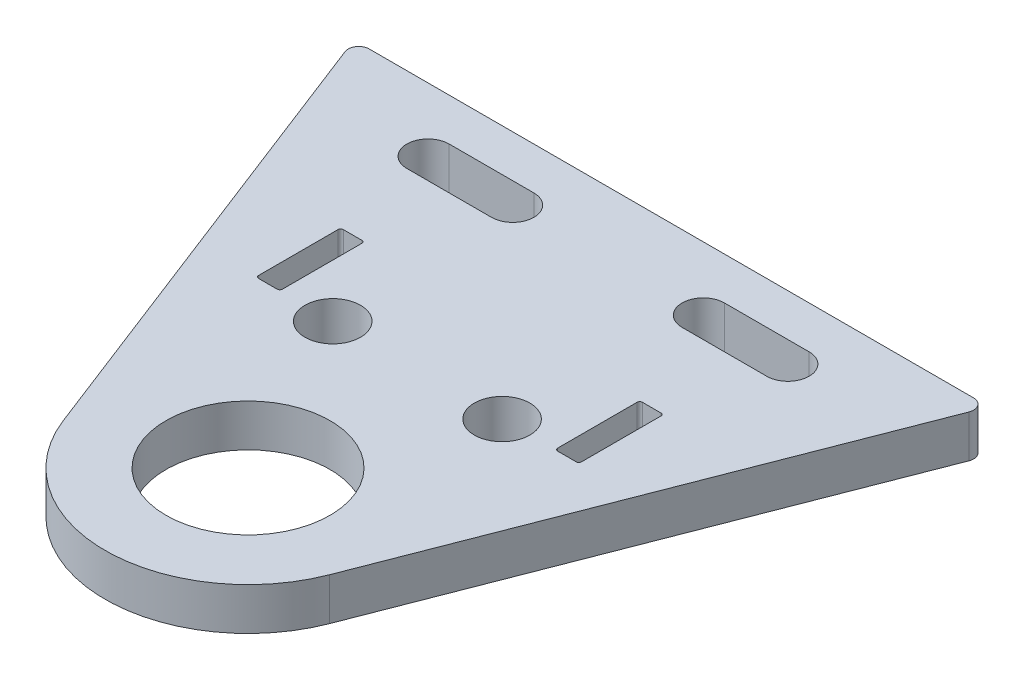
SolidWorks part; units mm, degrees
material "Plain Carbon Steel"
ref_plane "Front" through (0, 0, 0) normal (0, 0, 1) x (1, 0, 0)
ref_plane "Top" through (0, 0, 0) normal (0, 1, 0) x (1, 0, 0)
ref_plane "Right" through (0, 0, 0) normal (1, 0, 0) x (0, 0, -1)
sketch "Sketch1" plane through (0, 0, 0) normal (0, 1, 0) x (1, 0, 0)
  line L0 (-95.25, 0) -> (95.25, 0)
  line L1 (-95.25, 0) -> (-39.9602, -142.5041)
  line L2 (95.25, 0) -> (39.9602, -142.5041)
  arc A0 (-39.9602, -142.5041) -> (39.9602, -142.5041) centre (0, -127) ccw
  point P1 (0, 0)
  dimension "D2" = 85.725
  dimension "D1" = 190.5
  dimension "D3" = 127
base flange "Base-Flange1" sketch "Sketch1" thickness 12.7 reverse thickness direction no parameters "D1"=15.621
sketch "Sketch2" plane through (0, 0, 0) normal (0, 1, 0) x (1, 0, 0)
  circle A0 centre (0, -127) radius 24.6063
  arc A1 (-39.9602, -142.5041) -> (39.9602, -142.5041) centre (0, -127) ccw construction
  circle A2 centre (-25.4, -76.2) radius 8.3312
  circle A3 centre (25.4, -76.2) radius 8.3312
  dimension "D2" = 49.2125
  dimension "D6" = 16.6624
  dimension "D3" = 50.8
  dimension "D4" = 25.4
  dimension "D5" = 25.4
extrude "Cut-Extrude1" cut sketch "Sketch2" against normal through all normal cut yes
sketch "Sketch7" plane through (0, 0, 0) normal (0, 1, 0) x (1, 0, 0)
  line L0 (53.975, -19.05) -> (28.575, -19.05) construction
  line L1 (53.975, -25.4) -> (28.575, -25.4)
  line L2 (53.975, -12.7) -> (28.575, -12.7)
  line L3 (-28.575, -19.05) -> (-53.975, -19.05) construction
  line L6 (-28.575, -25.4) -> (-53.975, -25.4)
  line L7 (-28.575, -12.7) -> (-53.975, -12.7)
  line L8 (95.25, 0) -> (-95.25, 0) construction
  arc A3 (53.975, -25.4) -> (53.975, -12.7) centre (53.975, -19.05) ccw
  arc A4 (28.575, -12.7) -> (28.575, -25.4) centre (28.575, -19.05) ccw
  arc A7 (-28.575, -25.4) -> (-28.575, -12.7) centre (-28.575, -19.05) ccw
  arc A8 (-53.975, -12.7) -> (-53.975, -25.4) centre (-53.975, -19.05) ccw
  point P2 (41.275, -19.05)
  point P10 (-41.275, -19.05)
  dimension "D4" = 28.575
  dimension "D2" = 6.35
  dimension "D3" = 6.35
  dimension "D1" = 19.05
  dimension "D5" = 28.575
  dimension "D6" = 25.4
  dimension "D7" = 25.4
extrude "Cut-Extrude2" cut sketch "Sketch7" against normal through all normal cut yes
fillet "Fillet1" radius 3.175 2 edges at (-95.25, -6.35, 0) (95.25, -6.35, 0)
sketch "Sketch8" plane through (0, 0, 0) normal (0, 1, 0) x (1, 0, 0)
  line L0 (41.275, -50.8) -> (-41.275, -50.8) construction
  line L1 (48.4187, -76.2) -> (41.275, -76.2)
  line L2 (48.4187, -76.2) -> (48.4187, -50.8)
  line L3 (48.4187, -50.8) -> (41.275, -50.8)
  line L4 (41.275, -76.2) -> (41.275, -50.8)
  line L5 (48.4187, -76.2) -> (41.275, -50.8) construction
  line L6 (48.4187, -50.8) -> (41.275, -76.2) construction
  line L7 (-41.275, -76.2) -> (-48.4187, -76.2)
  line L8 (-41.275, -76.2) -> (-41.275, -50.8)
  line L9 (-41.275, -50.8) -> (-48.4187, -50.8)
  line L10 (-48.4187, -76.2) -> (-48.4187, -50.8)
  line L11 (-41.275, -76.2) -> (-48.4187, -50.8) construction
  line L12 (-41.275, -50.8) -> (-48.4187, -76.2) construction
  point P0 (44.8469, -63.5)
  point P5 (-44.8469, -63.5)
  point P13 (0, -50.8)
  dimension "D1" = 25.4
  dimension "D2" = 25.4
  dimension "D3" = 50.8
  dimension "D4" = 50.8
  dimension "D5" = 7.1437
  dimension "D6" = 7.1437
  dimension "D7" = 82.55
extrude "Cut-Extrude3" cut sketch "Sketch8" along direction (0, 1, 0) on the side against the normal through all normal cut yes
fillet "Fillet2" radius 0.7937 8 edges at (-48.4187, -6.35, 50.8) (-41.275, -6.35, 50.8) (-48.4187, -6.35, 76.2) (-41.275, -6.35, 76.2) (48.4187, -6.35, 76.2) (41.275, -6.35, 76.2) (41.275, -6.35, 50.8) (48.4187, -6.35, 50.8)
sketch "Bend-Lines1" [suppressed] plane through (0, 0, 0) normal (0, 1, 0) x (1, 0, 0)
sketch "Bounding-Box1" [suppressed] plane through (0, 0, 0) normal (0, 1, 0) x (1, 0, 0)
sheet metal parameters "Sheet-Metal30" thickness 12.7 parameters "D1"=15.621
flat pattern "Flat-Pattern30" [suppressed]
sketch "Bend-Lines2" plane through (0, 0, 0) normal (0, 1, 0) x (1, 0, 0)
sketch3d "Bounding-Box2" [suppressed]
  line L0 (-95.25, 177.8, 0) -> (-95.25, -42.8625, 0) construction
  line L1 (95.25, 177.8, 0) -> (95.25, -42.8625, 0) construction
  line L2 (-95.25, 177.8, 0) -> (95.25, 177.8, 0) construction
  line L3 (-95.25, -42.8625, 0) -> (95.25, -42.8625, 0) construction
sheet metal parameters "Sheet-Metal31" thickness 12.7 parameters "D1"=15.621
flat pattern "Flat-Pattern30"
sketch "Bend-Lines2" plane through (0, 0, 0) normal (0, 1, 0) x (1, 0, 0)
sketch3d "Bounding-Box2" [suppressed]
  line L0 (-95.25, 177.8, 0) -> (-95.25, -42.8625, 0) construction
  line L1 (95.25, 177.8, 0) -> (95.25, -42.8625, 0) construction
  line L2 (-95.25, 177.8, 0) -> (95.25, 177.8, 0) construction
  line L3 (-95.25, -42.8625, 0) -> (95.25, -42.8625, 0) construction
sheet metal parameters "Sheet-Metal32" thickness 12.7 parameters "D1"=15.621
flat pattern "Flat-Pattern30"
sketch "Bend-Lines2" plane through (0, 0, 0) normal (0, 1, 0) x (1, 0, 0)
sketch3d "Bounding-Box2" [suppressed]
  line L0 (-94.2185, 177.8, 0) -> (-94.2185, -42.8625, 0) construction
  line L1 (94.2185, 177.8, 0) -> (94.2185, -42.8625, 0) construction
  line L2 (-94.2185, 177.8, 0) -> (94.2185, 177.8, 0) construction
  line L3 (-94.2185, -42.8625, 0) -> (94.2185, -42.8625, 0) construction
sheet metal parameters "Sheet-Metal34" thickness 12.7 parameters "D1"=15.621
flat pattern "Flat-Pattern30"
sketch "Bend-Lines2" plane through (0, 0, 0) normal (0, 1, 0) x (1, 0, 0)
sketch3d "Bounding-Box2" [suppressed]
  line L0 (93.7874, -42.8625, 0) -> (-93.7875, -42.8625, 0) construction
  line L1 (93.7874, 127, 0) -> (-93.7875, 127, 0) construction
  line L2 (93.7874, -42.8625, 0) -> (93.7874, 127, 0) construction
  line L3 (-93.7875, -42.8625, 0) -> (-93.7875, 127, 0) construction
equation "\"Total Cutting Length\"= \"Cutting Length-Outer\" + \"Cutting Length-Inner\""
equation "\"Amount in ft^2\"= \"Bounding Box Area-Blank\" / 144"
